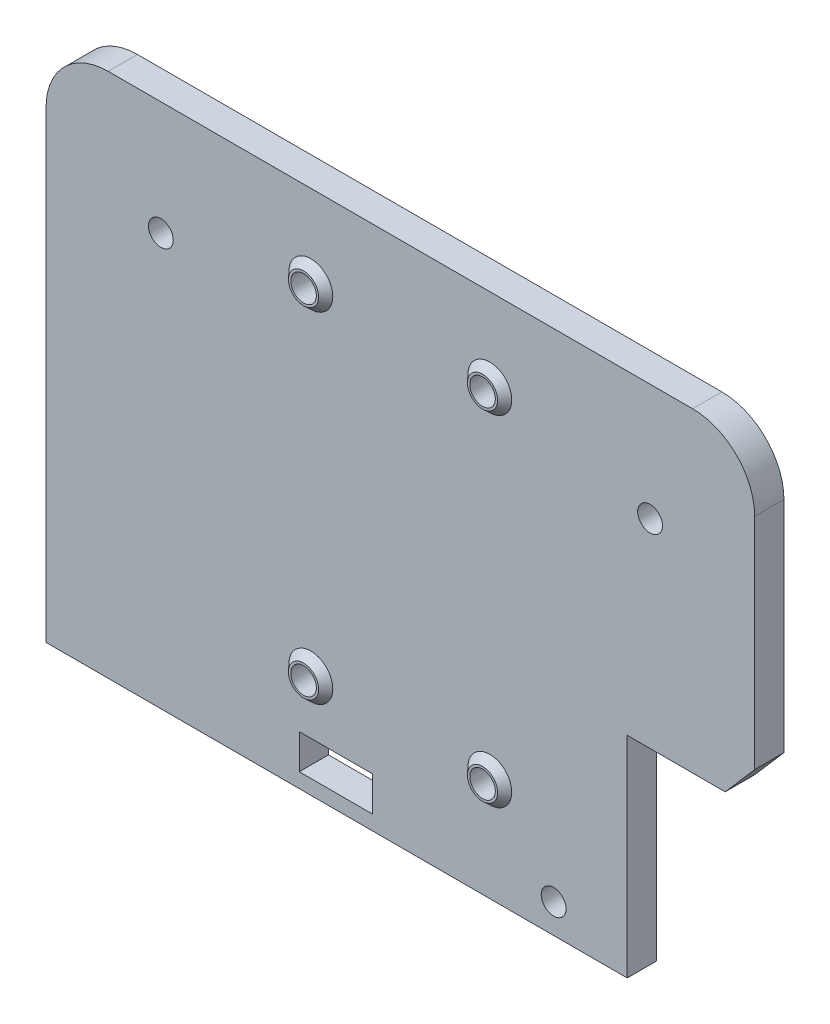
SolidWorks part; units mm, degrees
ref_plane "Alzado" through (0, 0, 0) normal (0, 0, 1) x (1, 0, 0)
ref_plane "Planta" through (0, 0, 0) normal (0, 1, 0) x (1, 0, 0)
ref_plane "Vista lateral" through (0, 0, 0) normal (1, 0, 0) x (0, 0, -1)
sketch "Croquis1" plane through (0, 0, 0) normal (0, 0, 1) x (1, 0, 0)
  line L0 (46.7611, -19.4581) -> (46.7611, -23.4581) construction
  line L1 (46.7611, -23.4581) -> (56.8328, -23.4581)
  line L2 (56.8328, -23.4581) -> (56.8328, 5.3147)
  line L4 (74.283, 40) -> (74.283, 9.9744)
  line L5 (74.283, 40) -> (65.783, 40) construction
  line L6 (65.783, 40) -> (65.783, 48.5) construction
  line L7 (65.783, 48.5) -> (-14.217, 48.5)
  line L8 (-14.217, 48.5) -> (-14.217, 40) construction
  line L9 (-14.217, 40) -> (-22.717, 40) construction
  line L10 (-22.717, 40) -> (-22.717, -23.4581)
  line L11 (-22.717, -23.4581) -> (46.7611, -23.4581)
  line L12 (70.2452, 5.3147) -> (74.283, 9.9744)
  line L13 (56.8328, 5.3147) -> (70.2452, 5.3147)
  line L19 (11.9402, -21.4537) -> (21.9984, -21.4537)
  line L20 (11.9402, -21.4537) -> (11.9402, -16.6946)
  line L21 (11.9402, -16.6946) -> (21.9984, -16.6946)
  line L22 (21.9984, -21.4537) -> (21.9984, -16.6946)
  circle A0 centre (46.7611, -19.4581) radius 1.7
  arc A1 (-14.217, 48.5) -> (-22.717, 40) centre (-14.217, 40) ccw
  arc A2 (74.283, 40) -> (65.783, 48.5) centre (65.783, 40) ccw
  circle A3 centre (-7.0063, 32.9387) radius 1.7
  circle A4 centre (59.9647, 32.5582) radius 1.7
  point P9 (70.2452, 5.3147)
  point P26 (73.8536, 9.9744)
  point P27 (71.2887, 3.9706)
  point P28 (70.8157, 4.5754)
  dimension "D2" = 3.4
  dimension "D1" = 4
  dimension "D3" = 8.5
extrude "Saliente-Extruir1" add sketch "Croquis1" along normal blind 4
sketch "Croquis2" plane through (0, 0, 4) normal (0, 0, 1) x (1, 0, 0)
  circle A0 centre (13.5276, 37.1561) radius 1.75
  circle A1 centre (38.0276, 37.1561) radius 1.75
  circle A2 centre (13.5276, -9.3439) radius 1.75
  circle A3 centre (38.0276, -9.3439) radius 1.75
  circle A4 centre (13.5276, 37.1561) radius 3
  circle A5 centre (38.0276, 37.1561) radius 3
  circle A6 centre (38.0276, -9.3439) radius 3
  circle A7 centre (13.5276, -9.3439) radius 3
extrude "Saliente-Extruir2" add sketch "Croquis2" along normal blind 1
chamfer "Chaflán1" distance 1 angle 43 4 edges at (41.0276, 37.1561, 5) (16.5276, 37.1561, 5) (16.5276, -9.3439, 5) (41.0276, -9.3439, 5) first distance on face at (41.0276, 37.1561, 5) first distance on face at (16.5276, 37.1561, 5) first distance on face at (16.5276, -9.3439, 5) first distance on face at (41.0276, -9.3439, 5)
sketch "Croquis3" plane through (0, 0, 4) normal (0, 0, 1) x (1, 0, 0)
  circle A1 centre (13.5276, -9.3439) radius 1.75
  circle A2 centre (13.5276, -9.3439) radius 1.75
  circle A3 centre (38.0276, -9.3439) radius 1.75
  circle A4 centre (38.0276, -9.3439) radius 1.75
  circle A5 centre (38.0276, 37.1561) radius 1.75
  circle A6 centre (38.0276, 37.1561) radius 1.75
  circle A7 centre (13.5276, 37.1561) radius 1.75
  circle A8 centre (13.5276, 37.1561) radius 1.75
  dimension "D1" = 0
  dimension "D2" = 0
  dimension "D3" = 0
  dimension "D4" = 0
extrude "Cortar-Extruir1" cut sketch "Croquis3" against normal blind 6
sketch "Croquis5" plane through (0, 0, 0) normal (0, 0, -1) x (-1, 0, 0)
  line L0 (-13.5283, -9.3362) -> (-37.9938, -9.3362) construction
  line L1 (-13.5283, -12.6559) -> (-10.6533, -10.9961)
  line L2 (-10.6533, -10.9961) -> (-10.6533, -7.6763)
  line L3 (-10.6533, -7.6763) -> (-13.5283, -6.0164)
  line L4 (-13.5283, -6.0164) -> (-16.4033, -7.6763)
  line L5 (-16.4033, -7.6763) -> (-16.4033, -10.9961)
  line L6 (-16.4033, -10.9961) -> (-13.5283, -12.6559)
  line L7 (-13.5283, -9.3362) -> (-13.5283, 37.1855) construction
  line L8 (-13.5283, 13.9247) -> (-26.5245, 13.9247) construction
  line L9 (-25.761, -9.3362) -> (-25.761, 3.1711) construction
  line L10 (-40.8688, -7.6763) -> (-37.9938, -6.0164)
  line L11 (-40.8688, -10.9961) -> (-40.8688, -7.6763)
  line L12 (-37.9938, -12.6559) -> (-40.8688, -10.9961)
  line L13 (-35.1188, -10.9961) -> (-37.9938, -12.6559)
  line L14 (-35.1188, -7.6763) -> (-35.1188, -10.9961)
  line L15 (-37.9938, -6.0164) -> (-35.1188, -7.6763)
  line L16 (-40.8688, 38.8454) -> (-40.8688, 35.5257)
  line L17 (-37.9938, 40.5053) -> (-40.8688, 38.8454)
  line L18 (-35.1188, 38.8454) -> (-37.9938, 40.5053)
  line L19 (-35.1188, 35.5257) -> (-35.1188, 38.8454)
  line L20 (-37.9938, 33.8658) -> (-35.1188, 35.5257)
  line L21 (-40.8688, 35.5257) -> (-37.9938, 33.8658)
  line L22 (-16.4033, 35.5257) -> (-16.4033, 38.8454)
  line L23 (-13.5283, 33.8658) -> (-16.4033, 35.5257)
  line L24 (-10.6533, 35.5257) -> (-13.5283, 33.8658)
  line L25 (-10.6533, 38.8454) -> (-10.6533, 35.5257)
  line L26 (-13.5283, 40.5053) -> (-10.6533, 38.8454)
  line L27 (-16.4033, 38.8454) -> (-13.5283, 40.5053)
  circle A0 centre (-13.5283, -9.3362) radius 2.875 construction
  circle A1 centre (-37.9938, -9.3362) radius 2.875 construction
  point P14 (-37.9938, -9.3362)
  point P15 (-13.5283, 37.1855)
extrude "Cortar-Extruir2" cut sketch "Croquis5" against normal blind 2
sketch "Croquis6" plane through (0, 0, 2) normal (0, 0, -1) x (-1, 0, 0)
  line L0 (-13.5283, -12.6559) -> (-16.4033, -7.6763)
  line L1 (-13.5283, -6.0164) -> (-16.4033, -7.6763) construction
  line L2 (-16.4033, -7.6763) -> (-16.4033, -10.9961)
  line L3 (-16.4033, -7.6763) -> (-16.4033, -10.9961) construction
  line L4 (-16.4033, -10.9961) -> (-13.5283, -12.6559)
  line L5 (-10.6533, -10.9961) -> (-10.6533, -7.6763)
  line L6 (-10.6533, -10.9961) -> (-10.6533, -7.6763) construction
  line L7 (-10.6533, -7.6763) -> (-13.5283, -6.0164)
  line L8 (-10.6533, -7.6763) -> (-13.5283, -6.0164) construction
  line L9 (-13.5283, -6.0164) -> (-10.6533, -10.9961)
  line L10 (-38.0276, -9.3439) -> (-13.5276, -9.3439) construction
  line L11 (-13.5276, -9.3439) -> (-25.7776, -9.3439) construction
  line L12 (-25.7776, -9.3439) -> (-25.7776, 16.6119) construction
  line L13 (-25.7776, 16.6119) -> (-13.5276, -9.3439) construction
  line L14 (-13.5276, -9.3439) -> (-13.5276, 37.1561) construction
  line L15 (-13.5276, 37.1561) -> (-13.5276, 13.9061) construction
  line L16 (-16.4033, -10.9961) -> (-13.5283, -12.6559)
  line L17 (-13.5283, -12.6559) -> (-10.6533, -10.9961)
  line L18 (-10.6533, -10.9961) -> (-10.6533, -7.6763)
  line L19 (-10.6533, -7.6763) -> (-13.5283, -6.0164)
  line L20 (-13.5283, -6.0164) -> (-16.4033, -7.6763)
  line L21 (-16.4033, -7.6763) -> (-16.4033, -10.9961)
  line L22 (-16.4033, -10.9961) -> (-13.5283, -12.6559)
  line L23 (-13.5283, -12.6559) -> (-10.6533, -10.9961)
  line L24 (-10.6533, -10.9961) -> (-10.6533, -7.6763)
  line L25 (-10.6533, -7.6763) -> (-13.5283, -6.0164)
  line L26 (-13.5283, -6.0164) -> (-16.4033, -7.6763)
  line L27 (-16.4033, -7.6763) -> (-16.4033, -10.9961)
  line L28 (-13.5276, 13.9061) -> (-22.0419, 13.9061) construction
  line L29 (-38.0268, -12.6559) -> (-40.9018, -10.9961)
  line L30 (-38.0268, -6.0164) -> (-40.9018, -10.9961)
  line L31 (-38.0268, -6.0164) -> (-35.1518, -7.6763)
  line L32 (-38.0268, -12.6559) -> (-35.1518, -7.6763)
  line L33 (-13.5283, 33.8286) -> (-16.4033, 35.4885)
  line L34 (-13.5283, 33.8286) -> (-10.6533, 38.8082)
  line L35 (-13.5283, 40.4681) -> (-10.6533, 38.8082)
  line L36 (-13.5283, 40.4681) -> (-16.4033, 35.4885)
  line L37 (-38.0268, 33.8286) -> (-40.9018, 38.8082)
  line L38 (-38.0268, 40.4681) -> (-40.9018, 38.8082)
  line L39 (-38.0268, 40.4681) -> (-35.1518, 35.4885)
  line L40 (-38.0268, 33.8286) -> (-35.1518, 35.4885)
  circle M10 centre (-13.5276, -9.3439) radius 1.75
  line M12 (-13.5283, -12.6559) -> (-10.6533, -10.9961)
  line M15 (-13.5283, -6.0164) -> (-16.4033, -7.6763)
  dimension "D1" = 0
extrude "Cortar-Extruir3" cut sketch "Croquis6" against normal blind 0.2 contours L9 L0 M10 M12 | L9 L0 M15 M10 | L37 L40 L39 L38 | L35 L36 L33 L34 | L29 L32 L31 L30 region at (12.4667, -11.1711, 2) region at (14.5832, -7.5051, 2) region at (38.0268, -9.3362, 2) region at (13.5283, 37.1483, 2) region at (38.0268, 37.1483, 2)
sketch "Croquis7" plane through (0, 0, 2.2) normal (0, 0, -1) x (-1, 0, 0)
  line L0 (-14.3937, -7.8233) -> (-15.8421, -8.6483)
  line L1 (-15.2442, -9.6839) -> (-16.4033, -7.6763) construction
  line L2 (-14.3937, -7.8233) -> (-12.9623, -6.9968)
  line L3 (-13.5283, -6.0164) -> (-12.3596, -8.0408) construction
  line L4 (-12.012, -8.4689) -> (-15.0431, -10.2189) construction
  line L5 (-12.6438, -10.8543) -> (-11.2123, -10.0279)
  line L6 (-12.6438, -10.8543) -> (-14.0824, -11.6962)
  line L7 (-38.0276, -9.3439) -> (-13.5276, -9.3439) construction
  line L8 (-13.5276, -9.3439) -> (-25.7776, -9.3439) construction
  line L9 (-25.7776, -9.3439) -> (-25.7776, 5.9656) construction
  line L10 (-10.6533, -10.9961) -> (-11.815, -8.984)
  line L11 (-14.6803, -10.6606) -> (-13.5283, -12.6559)
  line L12 (-13.5283, -12.6559) -> (-10.6533, -10.9961)
  line L13 (-10.6533, -10.9961) -> (-11.815, -8.984)
  line L14 (-14.6803, -10.6606) -> (-13.5283, -12.6559)
  line L15 (-13.5283, -12.6559) -> (-10.6533, -10.9961)
  line L16 (-12.3596, -8.0408) -> (-13.5283, -6.0164)
  line L17 (-13.5283, -6.0164) -> (-16.4033, -7.6763)
  line L18 (-16.4033, -7.6763) -> (-15.2442, -9.6839)
  line L19 (-12.3596, -8.0408) -> (-13.5283, -6.0164)
  line L20 (-13.5283, -6.0164) -> (-16.4033, -7.6763)
  line L21 (-16.4033, -7.6763) -> (-15.2442, -9.6839)
  line L22 (-25.7776, 5.9656) -> (-13.5276, -9.3439) construction
  line L23 (-13.5276, -9.3439) -> (-13.5276, 37.1561) construction
  line L24 (-13.5276, 37.1561) -> (-13.5276, 13.9061) construction
  line L25 (-13.5276, 13.9061) -> (-20.5205, 13.9061) construction
  line L26 (-35.1518, -7.6763) -> (-36.3109, -9.6839)
  line L27 (-36.8748, -10.6606) -> (-38.0268, -12.6559)
  line L28 (-38.9114, -10.8543) -> (-37.4727, -11.6962)
  line L29 (-38.9114, -10.8543) -> (-40.3429, -10.0279)
  line L30 (-40.9018, -10.9961) -> (-39.7402, -8.984)
  line L31 (-39.1956, -8.0408) -> (-38.0268, -6.0164)
  line L32 (-37.1614, -7.8233) -> (-38.5929, -6.9968)
  line L33 (-37.1614, -7.8233) -> (-35.713, -8.6483)
  line L34 (-10.6533, 38.8082) -> (-11.815, 36.7961)
  line L35 (-12.6438, 38.6665) -> (-11.2123, 37.84)
  line L36 (-12.6438, 38.6665) -> (-14.0824, 39.5083)
  line L37 (-14.6803, 38.4728) -> (-13.5283, 40.4681)
  line L38 (-12.3596, 35.8529) -> (-13.5283, 33.8286)
  line L39 (-14.3937, 35.6355) -> (-12.9623, 34.809)
  line L40 (-16.4033, 35.4885) -> (-15.2442, 37.496)
  line L41 (-14.3937, 35.6355) -> (-15.8421, 36.4605)
  line L42 (-39.1956, 35.8529) -> (-38.0268, 33.8286)
  line L43 (-37.1614, 35.6355) -> (-38.5929, 34.809)
  line L44 (-37.1614, 35.6355) -> (-35.713, 36.4605)
  line L45 (-35.1518, 35.4885) -> (-36.3109, 37.496)
  line L46 (-36.8748, 38.4728) -> (-38.0268, 40.4681)
  line L47 (-38.9114, 38.6665) -> (-37.4727, 39.5083)
  line L48 (-38.9114, 38.6665) -> (-40.3429, 37.84)
  line L49 (-40.9018, 38.8082) -> (-39.7402, 36.7961)
  arc A0 (-12.3596, -8.0408) -> (-15.2442, -9.6839) centre (-13.5276, -9.3439) ccw construction
  arc A1 (-11.815, -8.984) -> (-12.3596, -8.0408) centre (-13.5276, -9.3439) ccw construction
  arc A2 (-15.2442, -9.6839) -> (-14.6803, -10.6606) centre (-13.5276, -9.3439) ccw construction
  arc A3 (-39.1956, -8.0408) -> (-36.3109, -9.6839) centre (-38.0276, -9.3439) cw
  arc A4 (-14.6803, -10.6606) -> (-11.815, -8.984) centre (-13.5276, -9.3439) ccw
  arc A5 (-14.6803, -10.6606) -> (-11.815, -8.984) centre (-13.5276, -9.3439) ccw
  arc A6 (-12.3596, -8.0408) -> (-15.2442, -9.6839) centre (-13.5276, -9.3439) ccw
  arc A7 (-12.3596, -8.0408) -> (-15.2442, -9.6839) centre (-13.5276, -9.3439) ccw
  arc A8 (-36.8748, -10.6606) -> (-39.7402, -8.984) centre (-38.0276, -9.3439) cw
  arc A9 (-14.6803, 38.4728) -> (-11.815, 36.7961) centre (-13.5276, 37.1561) cw
  arc A10 (-12.3596, 35.8529) -> (-15.2442, 37.496) centre (-13.5276, 37.1561) cw
  arc A11 (-39.1956, 35.8529) -> (-36.3109, 37.496) centre (-38.0276, 37.1561) ccw
  arc A12 (-36.8748, 38.4728) -> (-39.7402, 36.7961) centre (-38.0276, 37.1561) ccw
  line M12 (-12.3596, -8.0408) -> (-13.5283, -6.0164)
  line M14 (-16.4033, -7.6763) -> (-15.2442, -9.6839)
  arc M15 (-15.2442, -9.6839) -> (-12.3596, -8.0408) centre (-13.5276, -9.3439) cw
  dimension "D1" = 0
  dimension "D2" = 0
extrude "Cortar-Extruir4" cut sketch "Croquis7" against normal blind 0.2 contours L0 M15 M14 | L2 M15 M12 | A5 L5 L13 | A5 L14 L6 | L31 A3 L32 | L33 A3 L26 | L27 A8 L28 | L29 A8 L30 | A12 L48 L49 | A12 L46 L47 | A11 L44 L45 | A11 L42 L43 | L35 A9 L34 | L37 A9 L36 | L41 A10 L40 | L38 A10 L39 region at (15.3481, -8.7358, 2.2) region at (13.1324, -7.4668, 2.2) region at (11.7044, -9.9402, 2.2) region at (13.9112, -11.2246, 2.2) region at (38.4227, -7.4668, 2.2) region at (36.207, -8.7358, 2.2) region at (39.8508, -9.9402, 2.2) region at (37.6439, -11.2246, 2.2) region at (13.9112, 39.0368, 2.2) region at (11.7044, 37.7524, 2.2) region at (15.3481, 36.548, 2.2) region at (13.1324, 35.279, 2.2) region at (38.4227, 35.279, 2.2) region at (36.207, 36.548, 2.2) region at (37.6439, 39.0368, 2.2) region at (39.8508, 37.7524, 2.2)
